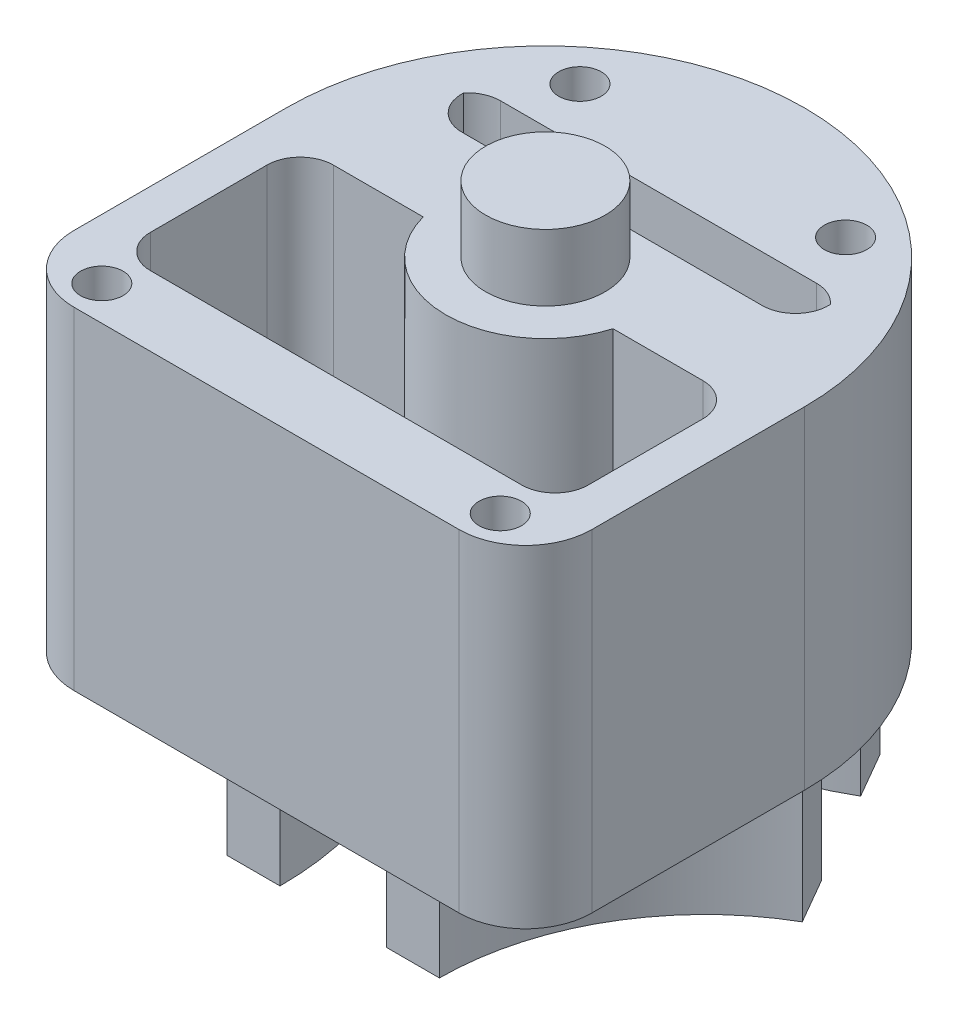
SolidWorks part; units mm, degrees
ref_plane "Front Plane" through (0, 0, 0) normal (0, 0, 1) x (1, 0, 0)
ref_plane "Top Plane" through (0, 0, 0) normal (0, 1, 0) x (1, 0, 0)
ref_plane "Right Plane" through (0, 0, 0) normal (1, 0, 0) x (0, 0, -1)
sketch "Sketch1" plane through (0, 0, 0) normal (0, 1, 0) x (1, 0, 0)
  circle A0 centre (0, 0) radius 28
  circle A1 centre (-28, -48.4974) radius 28
  circle A2 centre (28, -48.4974) radius 28
  arc A3 (-4.6726, -29.6339) -> (4.6726, -29.6339) centre (0, 0) ccw
  arc A4 (0, -37.7271) -> (-4.6726, -29.6339) centre (-28, -48.4974) ccw
  arc A5 (4.6726, -29.6339) -> (0, -37.7271) centre (28, -48.4974) ccw
  circle A6 centre (0, 0) radius 30 construction
  circle A7 centre (-28, -48.4974) radius 30 construction
  circle A8 centre (28, -48.4974) radius 30 construction
  circle A9 centre (0, 0) radius 24
  circle A10 centre (-28, -48.4974) radius 24
  circle A11 centre (28, -48.4974) radius 24
  circle A12 centre (0, 0) radius 20
  circle A13 centre (-28, -48.4974) radius 20
  circle A14 centre (28, -48.4974) radius 20
  dimension "D1" = 56
  dimension "D2" = 2
  dimension "D3" = 4
  dimension "D4" = 4
extrude "Boss-Extrude1" add sketch "Sketch1" along normal blind 10 contours A10 A13 | A9 A12 | A11 A14 | A5 A3 A4 region at (0, 0, 32.3316) region at (-23.3212, 0, 0) region at (-51.3212, 0, 48.4974) region at (4.6788, 0, 48.4974)
sketch "Sketch2" plane through (0, 10, 0) normal (0, 1, 0) x (1, 0, 0)
  line L0 (-19.5, -32.517) -> (-19.5, -53.517)
  line L1 (-19.5, -53.517) -> (19.5, -53.517)
  line L2 (19.5, -53.517) -> (19.5, -32.517)
  arc A0 (19.5, -32.517) -> (-19.5, -32.517) centre (0, -32.517) ccw
  dimension "D1" = 39
  dimension "D2" = 21
extrude "Boss-Extrude2" add sketch "Sketch2" along normal blind 25
sketch "Sketch3" plane through (0, 0, 0) normal (0, -1, 0) x (1, 0, 0)
  line L0 (0, 0) -> (28, 48.4974)
  line L1 (28, 48.4974) -> (-28, 48.4974)
  line L2 (-28, 48.4974) -> (0, 0)
  line L4 (-59.3942, 74.2986) -> (61.8263, 74.2986)
  line L5 (-59.3942, 74.2986) -> (-59.3942, -27.4652)
  line L6 (-59.3942, -27.4652) -> (61.8263, -27.4652)
  line L7 (61.8263, 74.2986) -> (61.8263, -27.4652)
  circle A0 centre (-28, 48.4974) radius 20 construction
  circle A1 centre (28, 48.4974) radius 20 construction
extrude "Cut-Extrude1" cut sketch "Sketch3" against normal blind 10
sketch "Sketch4" plane through (0, 35, 0) normal (0, 1, 0) x (1, 0, 0)
  line L0 (-10, -19.917) -> (10, -19.917) construction
  line L1 (-10, -18.317) -> (10, -18.317)
  line L2 (-10, -21.517) -> (10, -21.517)
  line L3 (-15, -50.917) -> (15, -50.917) construction
  line L4 (-15, -49.317) -> (15, -49.317)
  line L5 (-15, -52.517) -> (15, -52.517)
  circle A0 centre (0, -32.517) radius 4.5
  arc A1 (-10, -18.317) -> (-10, -21.517) centre (-10, -19.917) ccw
  arc A2 (10, -21.517) -> (10, -18.317) centre (10, -19.917) ccw
  arc A3 (-15, -49.317) -> (-15, -52.517) centre (-15, -50.917) ccw
  arc A4 (15, -52.517) -> (15, -49.317) centre (15, -50.917) ccw
  circle A5 centre (0, -32.517) radius 19.5 construction
  circle A6 centre (-10, -19.917) radius 1.6
  circle A7 centre (10, -19.917) radius 1.6
  circle A8 centre (-15, -50.917) radius 1.6
  circle A9 centre (15, -50.917) radius 1.6
  point P4 (0, -19.917)
  point P9 (0, -50.917)
  line M18 (-19.5, -53.517) -> (19.5, -53.517)
  dimension "D1" = 9
  dimension "D2" = 12.6
  dimension "D3" = 3.2
  dimension "D4" = 20
  dimension "D5" = 3.2
  dimension "D6" = 30
  dimension "D7" = 18.4
sketch "Sketch5" plane through (0, 35, 0) normal (0, 1, 0) x (1, 0, 0)
  line L7 (-13.596, -24) -> (13.596, -24)
  line L8 (13.596, -24) -> (15, -27.5)
  line L9 (15, -27.5) -> (-15, -27.5)
  line L10 (-15, -27.5) -> (-13.596, -24)
  arc A1 (-12, -20.7846) -> (12, -20.7846) centre (0, 0) ccw construction
  point P16 (-12.4447, -33.6914)
  dimension "D3" = 3.5
extrude "Cut-Extrude2" cut sketch "Sketch5" against normal up to surface (25 mm away) up to face at (-10.2237, 10, 38.2343)
fillet "Fillet2" radius 2.5 4 edges at (15, 22.5, 27.5) (-15, 22.5, 27.5) (13.596, 22.5, 24) (-13.596, 22.5, 24)
sketch "Sketch6" plane through (0, 10, 0) normal (0, -1, 0) x (1, 0, 0)
  line L1 (-9.9783, 39.8246) -> (-16.0405, 43.3246)
  line L2 (-11.4783, 37.2265) -> (-17.5405, 40.7265)
  line L3 (-16.0405, 43.3246) -> (-17.5405, 40.7265)
  line L6 (-9.9783, 39.8246) -> (-9.3884, 39.4841)
  line L7 (-11.4783, 37.2265) -> (-10.8884, 36.886)
  line L8 (-9.3884, 39.4841) -> (-10.8884, 36.886)
  line L9 (-10.1384, 38.185) -> (-7.2154, 36.4974)
  arc A0 (-18, 31.1769) -> (-8, 48.4974) centre (-28, 48.4974) ccw construction
  arc A1 (-16, 27.7128) -> (-4, 48.4974) centre (-28, 48.4974) ccw construction
  arc A2 (-18, 31.1769) -> (-8, 48.4974) centre (-28, 48.4974) ccw construction
  point P13 (-10.7283, 38.5256)
  dimension "D1" = 3
  dimension "D2" = 7
extrude "Boss-Extrude5" add sketch "Sketch6" along normal blind 7.5 contours L2 L3 L1 L6 L8 L7
chamfer "Chamfer1" distance 7.5 angle 43 1 edges at (-16.7905, 2.5, 42.0256) first distance on face at (-16.7905, 6.25, 42.0256)
ref_plane "Plane1" through (0, 0, 0) normal (-1, 0, 0) x (0, 0, 1)
mirror "Mirror1" about plane through (0, 0, 0) normal (-1, 0, 0) of "Chamfer1", "Boss-Extrude5"
sketch "Sketch7" plane through (0, 10, 0) normal (0, -1, 0) x (-1, 0, 0)
  line L0 (1.5, -20.1744) -> (-1.5, -20.1744)
  line L1 (1.5, -20.1744) -> (1.5, -13.1744)
  line L2 (-1.5, -20.1744) -> (-1.5, -13.1744)
  line L3 (1.5, -13.1744) -> (-1.5, -13.1744)
  arc A0 (19.5, -32.517) -> (-19.5, -32.517) centre (0, -32.517) ccw construction
  point P0 (0, -20.1744)
  point P3 (0, -13.017)
  point P6 (0, 0)
  dimension "D1" = 3
  dimension "D2" = 7
extrude "Boss-Extrude6" add sketch "Sketch7" along normal blind 7.5
chamfer "Chamfer2" distance 7 angle 45 1 edges at (0, 2.5, 13.1744)
fillet "Fillet4" radius 5 2 edges at (19.5, 22.5, 53.517) (-19.5, 22.5, 53.517)
extrude "Boss-Extrude7" add sketch "Sketch4" along normal blind 5 contours A0
extrude "Cut-Extrude3" cut sketch "Sketch4<3>" against normal blind 15 contours A1 A6 | A2 A7 | A8 A3 M18 | A4 A9 M18 region at (-10, 35, 19.917) region at (10, 35, 19.917) region at (-15, 35, 50.917) region at (15, 35, 50.917)
sketch "Sketch4<3>" plane through (0, 35, 0) normal (0, 1, 0) x (1, 0, 0) same geometry as "Sketch4"
sketch "Sketch8" plane through (0, 35, 0) normal (0, 1, 0) x (1, 0, 0)
  line L0 (-16.5, -34.4823) -> (-16.5, -48.2559)
  line L1 (-16.5, -48.2559) -> (16.4594, -48.2559)
  line L2 (16.4594, -48.2559) -> (16.4594, -34.6262)
  line L3 (16.4594, -34.6262) -> (7.1973, -34.6262)
  line L4 (-16.5, -34.4823) -> (-7.2379, -34.4823)
  line L5 (-19.5, -32.517) -> (-19.5, -48.517) construction
  arc A0 (-7.2379, -34.4823) -> (7.1973, -34.6262) centre (0, -32.517) ccw
  point P8 (-16.8155, -34.7175)
  dimension "D2" = 7.5
  dimension "D1" = 3
extrude "Cut-Extrude4" cut sketch "Sketch8" against normal blind 21
fillet "Fillet5" radius 2.5 4 edges at (16.4594, 24.5, 34.6262) (16.4594, 24.5, 48.2559) (-16.5, 24.5, 48.2559) (-16.5, 24.5, 34.4823)
sketch "Sketch9" plane through (0, 14, 0) normal (0, 1, 0) x (1, 0, 0)
  line L0 (-1.5, -48.2559) -> (1.5, -48.2559)
  line L1 (-1.5, -48.2559) -> (-1.5, -39.4989)
  line L2 (1.5, -48.2559) -> (1.5, -39.4989)
  line L3 (-1.5, -39.4989) -> (1.5, -39.4989)
  line L4 (-14, -48.2559) -> (13.9594, -48.2559) construction
  line L5 (-14, -48.2559) -> (13.9594, -48.2559) construction
  point P8 (0, -32.517)
  point P9 (0, -39.4989)
  point P11 (0, 0)
  dimension "D1" = 3
extrude "Boss-Extrude8" add sketch "Sketch9" along normal blind 10
